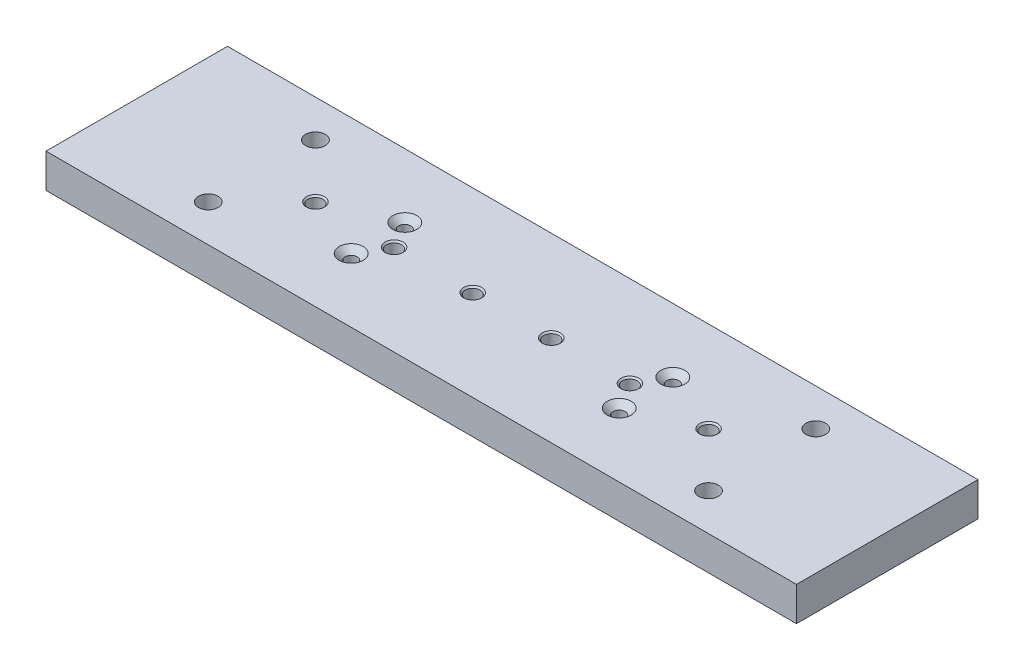
SolidWorks part; units mm, degrees
material "6061-T6 (SS)"
ref_plane "Front" through (0, 0, 0) normal (0, 0, 1) x (1, 0, 0)
ref_plane "Top" through (0, 0, 0) normal (0, 1, 0) x (1, 0, 0)
ref_plane "Right" through (0, 0, 0) normal (1, 0, 0) x (0, 0, -1)
sketch "Sketch1" plane through (0, 0, 0) normal (0, 1, 0) x (1, 0, 0)
  line L0 (0, 12.5629) -> (0, -12.5629) construction
  line L1 (-105, -25.4) -> (105, -25.4)
  line L2 (-105, -25.4) -> (-105, 25.4)
  line L3 (-105, 25.4) -> (105, 25.4)
  line L4 (105, -25.4) -> (105, 25.4)
  line L5 (-105, -25.4) -> (105, 25.4) construction
  line L6 (-105, 25.4) -> (105, -25.4) construction
  line L7 (-55, -20) -> (55, -20) construction
  line L8 (-55, -20) -> (-55, 20) construction
  line L9 (-55, 20) -> (55, 20) construction
  line L10 (55, -20) -> (55, 20) construction
  line L11 (-55, -20) -> (55, 20) construction
  line L12 (-55, 20) -> (55, -20) construction
  line L13 (-80, 25.4) -> (-60, 25.4) construction
  line L14 (-80, 25.4) -> (-80, -25.4) construction
  line L15 (-80, -25.4) -> (-60, -25.4) construction
  line L16 (-60, 25.4) -> (-60, -25.4) construction
  line L17 (60, 25.4) -> (60, -25.4) construction
  line L18 (80, -25.4) -> (60, -25.4) construction
  line L19 (80, 25.4) -> (80, -25.4) construction
  line L20 (80, 25.4) -> (60, 25.4) construction
  point P0 (0, 0)
  point P6 (0, 0)
  dimension "D1" = 40
  dimension "D2" = 110
  dimension "D3" = 50.8
  dimension "D4" = 20
  dimension "D5" = 5
  dimension "D6" = 25
extrude "Boss-Extrude1" add sketch "Sketch1" along normal blind 9.525
hole_wizard "CSK for M3 SFHCS1" positions "Sketch2" profile "Sketch3" countersink size "M3" standard "ANSI Metric" end condition through all
sketch "Sketch2" plane through (0, 9.525, 0) normal (0, 1, 0) x (1, 0, 0)
  line L0 (-37.5, 7.5) -> (37.5, -7.5) construction
  line L2 (-55, -20) -> (-55, 20) construction
  point P1 (-37.5, 7.5)
  point P3 (-37.5, -7.5)
  point P5 (37.5, -7.5)
  point P7 (37.5, 7.5)
  dimension "D1" = 15
  dimension "D2" = 17.5
sketch "Sketch3" plane through (-37.5, 9.525, -7.5) normal (1, 0, 0) x (0, 0, 1)
  line L0 (0, 0) -> (0, 9.525)
  line L1 (0, 9.525) -> (1.7, 9.525)
  line L2 (1.7, 9.525) -> (1.7, 1.66)
  line L3 (1.7, 1.66) -> (3.36, 0)
  line L5 (3.36, 0) -> (0, 0)
  line L6 (-1.7, 1.66) -> (-3.36, 0) construction
  line L11 (0, -6.35) -> (0, 107.95) construction
  dimension "Thru Hole Dia." = 3.4
  dimension "Thru Hole Depth" = 9.525
  dimension "Near C'Sink Dia." = 6.72
  dimension "Near C'Sink Angle" = 90
hole_wizard "M5 Clearance Hole2" positions "Sketch4" profile "Sketch5" hole size "M5" standard "ANSI Metric" end condition through all
sketch "Sketch4" plane through (0, 9.525, 0) normal (0, 1, 0) x (1, 0, 0)
  line L0 (-80, 0) -> (-60, 0)
  line L1 (-80, 25.4) -> (-80, -25.4) construction
  line L2 (-60, 25.4) -> (-60, -25.4) construction
  line L4 (-70, 15) -> (-70, -15)
  point P9 (-70, 15)
  point P10 (-70, -15)
  point P13 (-70, 0)
  dimension "D1" = 30
sketch "Sketch5" plane through (-70, 9.525, 15) normal (1, 0, 0) x (0, 0, 1)
  line L0 (0, 0) -> (0, 9.525)
  line L1 (0, 9.525) -> (2.75, 9.525)
  line L2 (2.75, 9.525) -> (2.75, 0)
  line L5 (2.75, 0) -> (0, 0)
  line L11 (0, -6.35) -> (0, 107.95) construction
  dimension "Thru Hole Dia." = 5.5
  dimension "Thru Hole Depth" = 9.525
mirror "Mirror1" about plane through (0, 0, 0) normal (1, 0, 0) of "M5 Clearance Hole2"
hole_wizard "M5x0.8 Tapped Hole1" positions "Sketch6" profile "Sketch8" tap size "M5x0.8" standard "ANSI Metric" end condition through all
sketch "Sketch6" plane through (0, 9.525, 0) normal (0, 1, 0) x (1, 0, 0)
  point P0 (-55, 0)
  point P7 (-33, 0)
  point P8 (-11, 0)
  point P9 (11, 0)
  point P10 (33, 0)
  point P11 (55, 0)
  dimension "D2" = 55
  dimension "D3" = 55
  dimension "D1" = 6
sketch "Sketch8" plane through (-55, 9.525, 0) normal (1, 0, 0) x (0, 0, 1)
  line L0 (0, 0) -> (0, 9.525)
  line L1 (0, 9.525) -> (2.1, 9.525)
  line L2 (2.1, 9.525) -> (2.1, 0.425)
  line L3 (2.1, 0.425) -> (2.525, 0)
  line L5 (2.525, 0) -> (0, 0)
  line L6 (-2.1, 0.425) -> (-2.525, 0) construction
  line L11 (0, -6.35) -> (0, 107.95) construction
  dimension "Thru Tap Drill Dia." = 4.2
  dimension "Thru Tap Drill Depth" = 9.525
  dimension "Near C'Sink Dia." = 5.05
  dimension "Near C'Sink Angle" = 90
cosmetic thread "Hole Thread1" parameters "D2"=5
cosmetic thread "Hole Thread2" parameters "D2"=5
cosmetic thread "Hole Thread3" parameters "D2"=5
cosmetic thread "Hole Thread4" parameters "D2"=5
cosmetic thread "Hole Thread5" parameters "D2"=5
cosmetic thread "Hole Thread6" parameters "D2"=5
